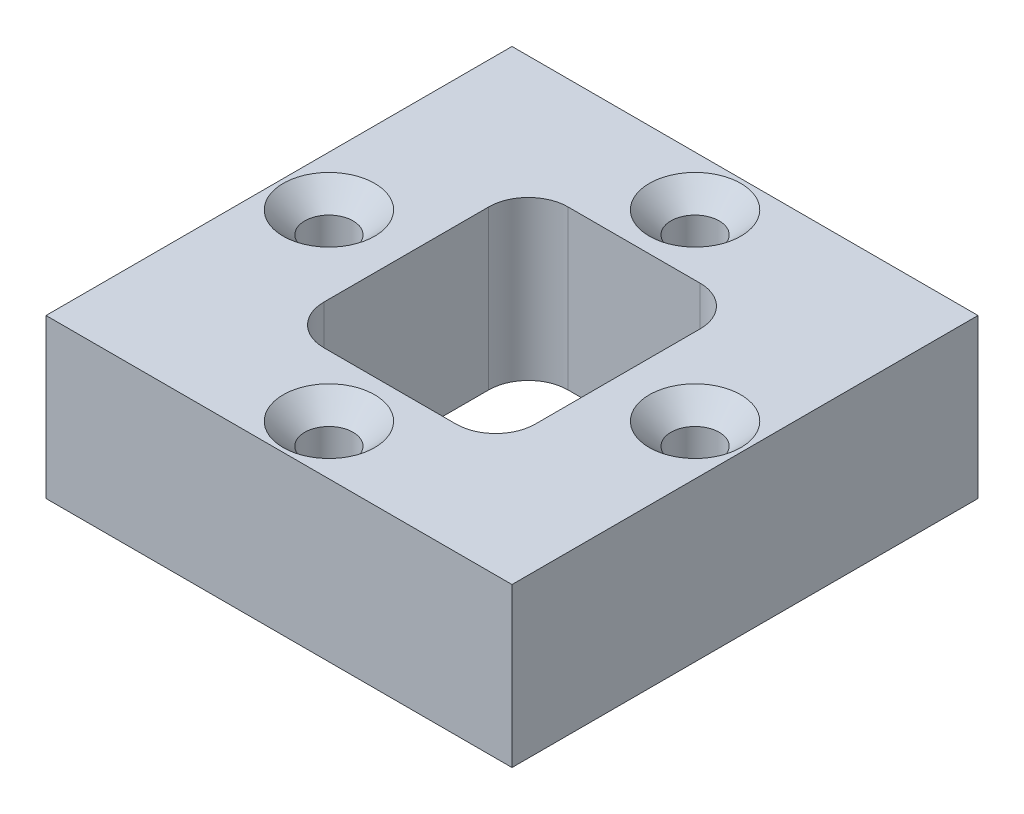
SolidWorks part; units mm, degrees
material "6061-T6 (SS)"
ref_plane "Front Plane" through (0, 0, 0) normal (0, 0, 1) x (1, 0, 0)
ref_plane "Top Plane" through (0, 0, 0) normal (0, 1, 0) x (1, 0, 0)
ref_plane "Right Plane" through (0, 0, 0) normal (1, 0, 0) x (0, 0, -1)
sketch "Sketch2" plane through (0, 0, 0) normal (0, 1, 0) x (1, 0, 0)
  line L1 (14, -14) -> (-14, -14)
  line L2 (14, -14) -> (14, 14)
  line L3 (14, 14) -> (-14, 14)
  line L4 (-14, -14) -> (-14, 14)
  line L5 (14, -14) -> (-14, 14) construction
  line L6 (14, 14) -> (-14, -14) construction
  point P0 (0, 0)
  dimension "D1" = 28
  dimension "D2" = 28
extrude "Boss-Extrude1" add sketch "Sketch2" along normal blind 9.525
sketch "Sketch6" plane through (0, 9.525, 0) normal (0, 1, 0) x (1, 0, 0)
  line L1 (6.35, -7.3323) -> (-6.35, -7.3323)
  line L2 (6.35, -7.3323) -> (6.35, 7.3323)
  line L3 (6.35, 7.3323) -> (-6.35, 7.3323)
  line L4 (-6.35, -7.3323) -> (-6.35, 7.3323)
  line L5 (6.35, -7.3323) -> (-6.35, 7.3323) construction
  line L6 (6.35, 7.3323) -> (-6.35, -7.3323) construction
  point P0 (0, 0)
  dimension "D1" = 14.6647
  dimension "D2" = 12.7
extrude "Cut-Extrude3" cut sketch "Sketch6" against normal up to surface (9.525 mm away) up to face at (0, 0, 0)
fillet "Fillet1" radius 2.3813 4 edges at (-6.35, 4.7625, -7.3323) (6.35, 4.7625, -7.3323) (6.35, 4.7625, 7.3323) (-6.35, 4.7625, 7.3323)
sketch "Sketch7" plane through (0, 9.525, 0) normal (0, 1, 0) x (1, 0, 0)
  line L0 (0, 0) -> (0, 14) construction
  line L1 (14, 14) -> (-14, 14) construction
  point P6 (0, 11)
  point P9 (-11, 0)
  point P10 (0, -11)
  point P11 (11, 0)
  point P12 (0, 0)
  dimension "D1" = 11
  dimension "D2" = 4
hole_wizard "CSK for M2.5 Flat Head Machine Screw1" positions "Sketch8" profile "Sketch9" countersink size "M2.5" standard "ANSI Metric"
sketch "Sketch8" plane through (0, 9.525, 0) normal (0, 1, 0) x (1, 0, 0)
  point P0 (-11, 0)
  point P3 (0, -11)
  point P6 (11, 0)
  point P9 (0, 11)
sketch "Sketch9" plane through (-11, 9.525, 0) normal (1, 0, 0) x (0, 0, 1)
  line L0 (0, 0) -> (0, 11.0312)
  line L1 (0, 11.0312) -> (1.45, 10.16)
  line L2 (1.45, 10.16) -> (1.45, 1.3)
  line L3 (1.45, 1.3) -> (2.75, 0)
  line L5 (2.75, 0) -> (0, 0)
  line L6 (-1.45, 1.3) -> (-2.75, 0) construction
  line L10 (0, 11.0312) -> (-1.45, 10.16) construction
  line L11 (0, -6.35) -> (0, 107.95) construction
  dimension "Hole Dia." = 2.9
  dimension "Hole Depth" = 10.16
  dimension "Near C'Sink Dia." = 5.5
  dimension "Near C'Sink Angle" = 90
  dimension "Drill Angle" = 118
